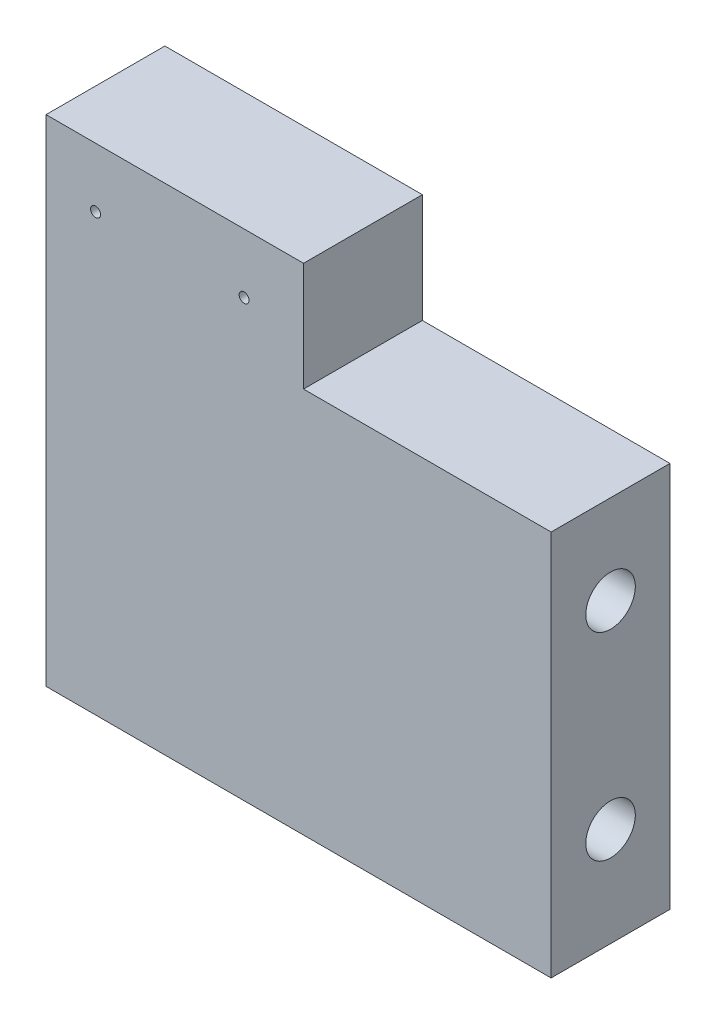
SolidWorks part; units mm, degrees
ref_plane "Front Plane" through (0, 0, 0) normal (0, 0, 1) x (1, 0, 0)
ref_plane "Top Plane" through (0, 0, 0) normal (0, 1, 0) x (1, 0, 0)
ref_plane "Right Plane" through (0, 0, 0) normal (1, 0, 0) x (0, 0, -1)
sketch "Sketch1" plane through (0, 0, 0) normal (0, 0, 1) x (1, 0, 0)
  line L1 (0, 0) -> (51, 0)
  line L2 (0, 0) -> (0, 50)
  line L3 (0, 50) -> (51, 50)
  line L4 (51, 0) -> (51, 50)
  dimension "D1" = 51
  dimension "D2" = 50
extrude "Boss-Extrude1" add sketch "Sketch1" along normal blind 12
sketch "Sketch2" plane through (0, 0, 0) normal (-1, 0, 0) x (0, 0, 1)
  line L0 (6, 50) -> (6, 0) construction
  line L1 (12, 50) -> (0, 50) construction
  line L2 (12, 0) -> (0, 0) construction
  circle A0 centre (6, 30) radius 2.5
  circle A1 centre (6, 10) radius 2.5
  dimension "D1" = 5
  dimension "D2" = 20
  dimension "D3" = 10
extrude "Cut-Extrude1" cut sketch "Sketch2" against normal up to next
sketch "Sketch3" plane through (0, 0, 0) normal (-1, 0, 0) x (0, 0, 1)
  circle A0 centre (6, 30) radius 5
  circle A1 centre (6, 10) radius 5
  dimension "D1" = 10
extrude "Cut-Extrude2" cut sketch "Sketch3" against normal blind 1.5
sketch "Sketch4" plane through (0, 0, 12) normal (0, 0, 1) x (1, 0, 0)
  line L0 (0, 44) -> (51, 44) construction
  line L1 (0, 50) -> (0, 0) construction
  line L2 (51, 0) -> (51, 50) construction
  line L3 (51, 50) -> (0, 50) construction
  line L4 (0, 0) -> (51, 0) construction
  line L6 (51, 50) -> (26, 50)
  line L7 (51, 50) -> (51, 39)
  line L8 (51, 39) -> (26, 39)
  line L9 (26, 50) -> (26, 39)
  circle A0 centre (5, 44) radius 0.5
  circle A1 centre (20, 44) radius 0.5
  point P20 (38.5, 39)
  dimension "D2" = 1
  dimension "D1" = 6
  dimension "D3" = 5
  dimension "D4" = 15
  dimension "D5" = 39
  dimension "D6" = 25
extrude "Cut-Extrude3" cut sketch "Sketch4" against normal up to next
